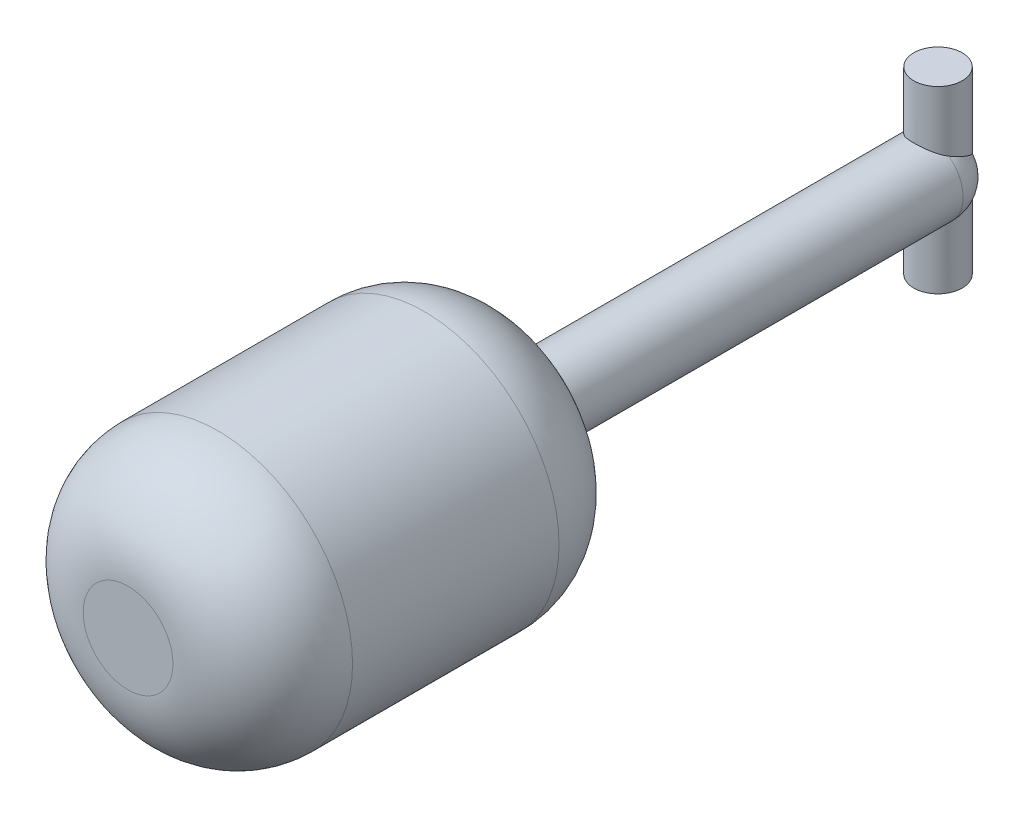
SolidWorks part; units mm, degrees
ref_plane "Спереди" through (0, 0, 0) normal (0, 0, 1) x (1, 0, 0)
ref_plane "Сверху" through (0, 0, 0) normal (0, 1, 0) x (1, 0, 0)
ref_plane "Справа" through (0, 0, 0) normal (1, 0, 0) x (0, 0, -1)
sketch "Sketch1" plane through (0, 0, 0) normal (0, 0, 1) x (1, 0, 0)
  circle A0 centre (0, 0) radius 4
  circle A1 centre (0, 0) radius 15
  circle A2 centre (0, 0) radius 12
extrude "Boss-Extrude1" add sketch "Sketch1" along normal blind 50 contours A0 region at (0, 0, 0)
extrude "Boss-Extrude2" add sketch "Sketch1<3>" along normal blind 40 from offset 50 separate body contours A1 A2 | A2 A0 | A0 region at (0, 0, 0) region at (-14.5757, 0, 0) region at (-11.6606, 0, 0)
sketch "Sketch1<3>" plane through (0, 0, 0) normal (0, 0, 1) x (1, 0, 0) same geometry as "Sketch1"
extrude "Boss-Extrude3" add sketch "Sketch1<4>" along normal blind 3 from offset 50 contours A2 A0 | A0 region at (0, 0, 0) region at (-11.6606, 0, 0)
sketch "Sketch1<4>" plane through (0, 0, 0) normal (0, 0, 1) x (1, 0, 0) same geometry as "Sketch1"
fillet "Fillet1" radius 10 1 edges at (15, 0, 50)
fillet "Fillet2" radius 10 rebuild error yes
extrude "Boss-Extrude4" add sketch "Sketch1<5>" along normal blind 3 from offset 90 contours A2 A0 | A1 A2 | A0 region at (0, 0, 0) region at (-14.5757, 0, 0) region at (-11.6606, 0, 0)
sketch "Sketch1<5>" plane through (0, 0, 0) normal (0, 0, 1) x (1, 0, 0) same geometry as "Sketch1"
fillet "Fillet5" radius 10 rebuild error yes
fillet "Fillet6" radius 10 1 edges at (15, 0, 93)
sketch "Sketch2" plane through (0, 0, 0) normal (0, 1, 0) x (1, 0, 0)
  circle A0 centre (0, -2.8) radius 2.7
extrude "Boss-Extrude5" add sketch "Sketch2" along normal blind 10 and the other way blind 10
fillet "Fillet7" radius 4 1 edges at (4, 0, 0)
